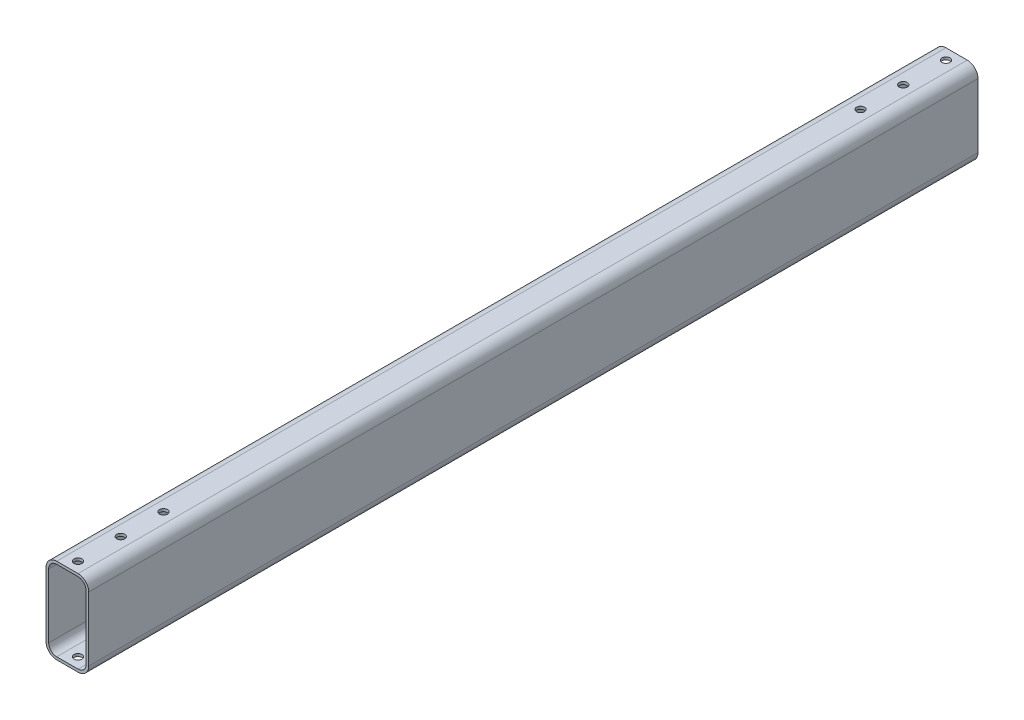
SolidWorks part; units mm, degrees
material "6061-T6 (SS)"
ref_plane "Front Plane" through (0, 0, 0) normal (0, 0, 1) x (1, 0, 0)
ref_plane "Top Plane" through (0, 0, 0) normal (0, 1, 0) x (1, 0, 0)
ref_plane "Right Plane" through (0, 0, 0) normal (1, 0, 0) x (0, 0, -1)
sketch "Sketch1" plane through (0, 0, 0) normal (0, 0, 1) x (1, 0, 0)
  line L1 (-6.35, -25.4) -> (6.35, -25.4)
  line L2 (-12.7, -19.05) -> (-12.7, 19.05)
  line L3 (-6.35, 25.4) -> (6.35, 25.4)
  line L4 (12.7, -19.05) -> (12.7, 19.05)
  line L5 (-12.7, -25.4) -> (12.7, 25.4) construction
  line L6 (-12.7, 25.4) -> (12.7, -25.4) construction
  arc A0 (-12.7, -19.05) -> (-6.35, -25.4) centre (-6.35, -19.05) ccw
  arc A1 (6.35, -25.4) -> (12.7, -19.05) centre (6.35, -19.05) ccw
  arc A2 (6.35, 25.4) -> (12.7, 19.05) centre (6.35, 19.05) cw
  arc A3 (-12.7, 19.05) -> (-6.35, 25.4) centre (-6.35, 19.05) cw
  point P0 (0, 0)
  dimension "D3" = 6.35
  dimension "D1" = 50.8
  dimension "D2" = 25.4
extrude "Extrude-Thin1" add sketch "Sketch1" along normal blind 528.701 thin thin type one direction reverse wall 1.5875
hole_wizard "3/16 (0.1875) Diameter Hole1" positions "3DSketch1" profile "Sketch3" hole size "3/16" standard "ANSI Inch" end condition through all
sketch3d "3DSketch1"
  line L1 (6.35, 25.4, 0) -> (-6.35, 25.4, 0) construction
  line L6 (0, 25.4, 528.701) -> (0, 25.4, 0) construction
  line L7 (6.35, 25.4, 528.701) -> (-6.35, 25.4, 528.701) construction
  point P57 (0, 25.4, 6.35)
  point P59 (0, 25.4, 31.75)
  point P61 (0, 25.4, 57.15)
  point P63 (0, 25.4, 496.951)
  point P65 (0, 25.4, 471.551)
  point P67 (0, 25.4, 522.351)
  dimension "D1" = 25.4
  dimension "D2" = 25.4
  dimension "D3" = 6.35
  dimension "D4" = 25.4
  dimension "D5" = 25.4
  dimension "D6" = 6.35
sketch "Sketch3" plane through (0, 25.4, 522.351) normal (1, 0, 0) x (0, 0, 1)
  line L0 (0, 0) -> (0, 50.8)
  line L1 (0, 50.8) -> (2.3812, 50.8)
  line L2 (2.3812, 50.8) -> (2.3812, 0)
  line L5 (2.3812, 0) -> (0, 0)
  line L11 (0, -6.35) -> (0, 107.95) construction
  dimension "Thru Hole Dia." = 4.7625
  dimension "Thru Hole Depth" = 50.8
hole_wizard "3/16 (0.195) Diameter Hole1" positions "Sketch4" profile "Sketch5" hole size "3/16" standard "ANSI Inch" end condition up to next
sketch "Sketch4" plane through (0, -25.4, 0) normal (0, -1, 0) x (-1, 0, 0)
  point P3 (3.175, -116.4957)
  point P6 (-3.175, -141.8957)
  point P9 (3.175, -167.2957)
  point P12 (-3.175, -192.6957)
  point P15 (-3.175, -345.0957)
  point P18 (3.175, -370.4957)
  point P21 (-3.175, -395.8957)
  point P24 (3.175, -421.2957)
sketch "Sketch5" plane through (-3.175, -25.4, 116.4957) normal (1, 0, 0) x (0, 0, -1)
  line L0 (0, 0) -> (0, 1.5875)
  line L1 (0, 1.5875) -> (2.4765, 1.5875)
  line L2 (2.4765, 1.5875) -> (2.4765, 0)
  line L5 (2.4765, 0) -> (0, 0)
  line L11 (0, -6.35) -> (0, 107.95) construction
  dimension "Thru Hole Dia." = 4.953
  dimension "Thru Hole Depth" = 1.5875
